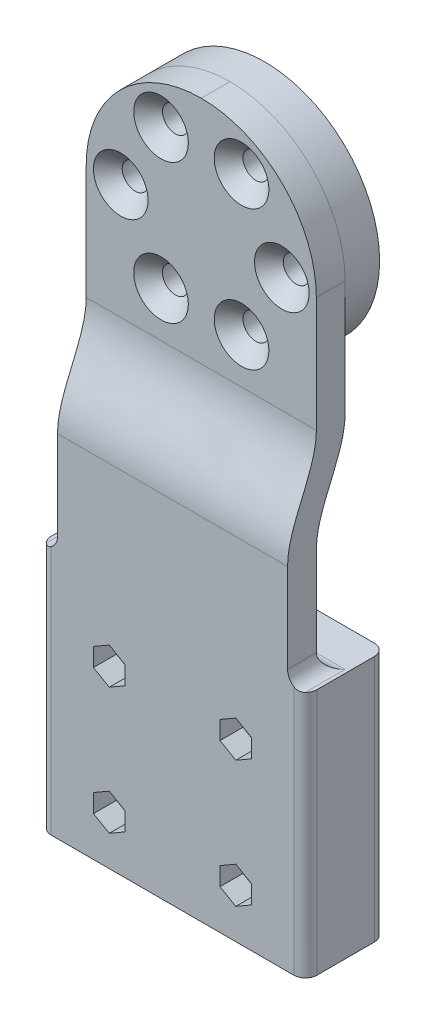
SolidWorks part; units mm, degrees
other "Markup1"
sketch "Sketch13" plane through (20, -53, 11) normal (0.0614, -0.6805, 0.7302) x (0.9699, -0.1321, -0.2046)
ref_plane "Front Plane" through (0, 0, 0) normal (0, 0, 1) x (1, 0, 0)
ref_plane "Top Plane" through (0, 0, 0) normal (0, 1, 0) x (1, 0, 0)
ref_plane "Right Plane" through (0, 0, 0) normal (1, 0, 0) x (0, 0, -1)
sketch "Sketch7" plane through (0, 0, 0) normal (0, 0, 1) x (1, 0, 0)
  line L1 (-20, 20) -> (20, 20)
  line L2 (-20, 20) -> (-20, -20)
  line L3 (-20, -20) -> (20, -20)
  line L4 (20, 20) -> (20, -20)
  line L5 (-20, 20) -> (20, -20) construction
  line L6 (-20, -20) -> (20, 20) construction
  point P0 (0, 0)
extrude "Boss-Extrude1" add sketch "Sketch7" along normal blind 11
ref_plane "Plane2" through (0, -21.4103, 5.7369) normal (0, -0.9659, 0.2588) x (1, 0, 0)
sketch "Sketch8" plane through (0, -20, 2.0782) normal (0, -1, 0) x (1, 0, 0)
  line L0 (20, 8.9218) -> (20, -2.0782) construction
  line L1 (-20, 8.9218) -> (20, 8.9218)
  line L2 (-20, 8.9218) -> (-20, 3.9218)
  line L3 (-20, 3.9218) -> (20, 3.9218)
  line L4 (20, 8.9218) -> (20, 3.9218)
  line L5 (0, 3.9218) -> (0, 8.9218) construction
  line L6 (-20, 6.4218) -> (20, 6.4218) construction
  line L7 (-20, -2.0782) -> (20, -2.0782) construction
  point P764 (0, 6.4218)
  dimension "D1" = 6
ref_plane "Plane4" through (0, -38, 0) normal (0, -1, 0) x (-1, 0, 0)
sketch "Sketch19" plane through (0, -38, 0) normal (0, -1, 0) x (-1, 0, 0)
  line L0 (20, -11) -> (20, 0) construction
  line L1 (20, -16) -> (-20, -16)
  line L2 (20, -16) -> (20, -11)
  line L3 (20, -11) -> (-20, -11)
  line L4 (-20, -16) -> (-20, -11)
  line L5 (20, -16) -> (-20, -11) construction
  line L6 (20, -11) -> (-20, -16) construction
  line L7 (-20, -11) -> (-20, 0) construction
  line L8 (20, -11) -> (-20, -11) construction
  point P4 (0, -13.5)
  dimension "D1" = 5
  dimension "D2" = 5
loft "Loft1" add profiles "Sketch19", "Sketch8" start constraint normal to profile start tangent length 1 end constraint normal to profile end tangent length 1 connector at (-20, -38, 16) connector at (-20, -20, 11)
sketch "Sketch16" plane through (0, 0, 0) normal (0, 0, -1) x (-1, 0, 0)
  line L1 (24.5131, 32.6211) -> (-24.5131, 32.6211)
  line L2 (24.5131, 32.6211) -> (24.5131, -32.6211)
  line L3 (24.5131, -32.6211) -> (-24.5131, -32.6211)
  line L4 (-24.5131, 32.6211) -> (-24.5131, -32.6211)
  line L5 (24.5131, 32.6211) -> (-24.5131, -32.6211) construction
  line L6 (24.5131, -32.6211) -> (-24.5131, 32.6211) construction
  circle A0 centre (0, 0) radius 20
extrude "Cut-Extrude3" cut sketch "Sketch16" against normal blind 6
ref_plane "Plane3" [suppressed] through (0, -56, 0) normal (0, -1, 0) x (-1, 0, 0)
sketch "Sketch17" plane through (0, -38, 0) normal (0, -1, 0) x (-1, 0, 0)
  line L1 (20, -16) -> (-20, -16)
  line L2 (20, -16) -> (20, -11)
  line L3 (20, -11) -> (-20, -11)
  line L4 (-20, -16) -> (-20, -11)
  line L5 (20, -16) -> (-20, -11) construction
  line L6 (20, -11) -> (-20, -16) construction
  line L10 (-20, -16) -> (20, -16) construction
  line L11 (-20, -6) -> (-20, -11) construction
  line L12 (20, -11) -> (20, -6) construction
  point P4 (0, -13.5)
  dimension "D1" = 5
extrude "Boss-Extrude5" add sketch "Sketch17" along normal blind 18
sketch "Sketch10" plane through (0, 0, 11) normal (0, 0, 1) x (1, 0, 0)
  circle A0 centre (-7.0001, 12.1244) radius 2.25
  circle A1 centre (6.9999, 12.1244) radius 2.25
  circle A2 centre (13.9999, 0.0001) radius 2.25
  circle A3 centre (6.9999, -12.1243) radius 2.25
  circle A4 centre (-7.0001, -12.1243) radius 2.25
  circle A5 centre (-14.0001, 0.0001) radius 2.25
  point P0 (0, 0)
  point P1 (0.0025, 0.0011)
  dimension "D4" = 4.5
extrude "Cut-Extrude1" cut sketch "Sketch10" against normal blind 25
sketch "Sketch11" plane through (0, -56, -3.473) normal (0, 1, 0) x (1, 0, 0)
  line L0 (20, -19.473) -> (-20, -19.473) construction
  line L5 (23.1, -5.473) -> (-23.1, -5.473)
  line L6 (23.1, -5.473) -> (23.1, -19.473)
  line L7 (23.1, -19.473) -> (-23.1, -19.473)
  line L8 (-23.1, -5.473) -> (-23.1, -19.473)
  line L9 (23.1, -5.473) -> (-23.1, -19.473) construction
  line L10 (23.1, -19.473) -> (-23.1, -5.473) construction
  line L16 (20, -14.473) -> (20, -19.473) construction
  point P0 (0, -12.473)
  point P7 (0, 0)
  point P8 (0, 0)
  point P9 (0, 0)
  dimension "D1" = 46.2
  dimension "D2" = 3.1
  dimension "D3" = 14
chamfer "Chamfer1" distance 2.5 angle 45 6 edges at (-4.7501, 12.1244, 11) (-11.7501, 0.0001, 11) (-4.7501, -12.1243, 11) (9.2499, 12.1244, 11) (16.2499, 0.0001, 11) (9.2499, -12.1243, 11)
fillet "Fillet3" radius 20 2 edges at (20, 20, 8.5) (-20, 20, 8.5)
extrude "Boss-Extrude6" add sketch "Sketch11" against normal blind 43
fillet "Fillet9" radius 2.5 3 edges at (0, -56, 11) (-20, -56, 13.5) (20, -56, 13.5)
ref_plane "Plane5" through (0, -99, 0) normal (0, -1, 0) x (-1, 0, 0)
sketch "Sketch20" plane through (0, -99, 0) normal (0, -1, 0) x (1, 0, 0)
  line L0 (0, 2) -> (0, 16) construction
  line L1 (20.3, 6.8) -> (-20.3, 6.8)
  line L2 (20.3, 6.8) -> (20.3, 11.2)
  line L3 (20.3, 11.2) -> (-20.3, 11.2)
  line L4 (-20.3, 6.8) -> (-20.3, 11.2)
  line L5 (20.3, 6.8) -> (-20.3, 11.2) construction
  line L6 (20.3, 11.2) -> (-20.3, 6.8) construction
  line L7 (23.1, 2) -> (-23.1, 2) construction
  line L8 (-23.1, 16) -> (23.1, 16) construction
  line L9 (-23.1, 2) -> (-23.1, 16) construction
  point P0 (0, 9)
  dimension "D1" = 4.4
  dimension "D2" = 40.6
  dimension "D3" = 23.1
  dimension "D4" = 7
extrude "Cut-Extrude4" cut sketch "Sketch20" against normal blind 40
sketch "Sketch22" plane through (0, 0, 0) normal (0, 0, 1) x (1, 0, 0)
  line L0 (-7.7, -99) -> (7.7, -99) construction
  line L1 (20, -99) -> (-20, -99)
  line L2 (20, -99) -> (20, -59)
  line L3 (20, -59) -> (-20, -59)
  line L4 (-20, -99) -> (-20, -59)
  line L5 (20, -99) -> (-20, -59) construction
  line L6 (20, -59) -> (-20, -99) construction
  line L9 (23.1, -99) -> (23.1, -56) construction
  circle A0 centre (-11, -68.5) radius 1.7
  circle A1 centre (11, -68.5) radius 1.7
  circle A2 centre (11, -90.5) radius 1.7
  circle A3 centre (-11, -90.5) radius 1.7
  point P0 (0, -79)
  point P7 (0, 0)
  point P10 (0, 0)
  point P11 (0, 0)
  point P14 (0, 0)
  dimension "D4" = 3.4
  dimension "D1" = 40
  dimension "D2" = 40
  dimension "D3" = 23.1
  dimension "D5" = 9.5
  dimension "D6" = 8.5
  dimension "D7" = 9
  dimension "D8" = 9
  dimension "D9" = 8.5
  dimension "D10" = 9
  dimension "D11" = 22
extrude "Cut-Extrude5" cut sketch "Sketch22" along normal blind 30 contours A1 | A2 | A3 | A0 region at (-11, -68.5, 0) region at (11, -68.5, 0) region at (11, -90.5, 0) region at (-11, -90.5, 0)
fillet "Fillet11" radius 2 4 edges at (-23.1, -77.5, 16) (-23.1, -77.5, 2) (23.1, -77.5, 16) (23.1, -77.5, 2)
ref_plane "Plane6" through (0, 0, 16) normal (0, 0, 1) x (1, 0, 0)
sketch "Sketch23" plane through (0, 0, 16) normal (0, 0, 1) x (1, 0, 0)
  line L0 (-13.75, -66.9123) -> (-8.25, -70.0877) construction
  line L1 (-11, -65.3246) -> (-13.75, -66.9123)
  line L2 (-13.75, -66.9123) -> (-13.75, -70.0877)
  line L3 (-13.75, -70.0877) -> (-11, -71.6754)
  line L4 (-11, -71.6754) -> (-8.25, -70.0877)
  line L5 (-8.25, -70.0877) -> (-8.25, -66.9123)
  line L6 (-8.25, -66.9123) -> (-11, -65.3246)
  line L7 (-11, -65.3246) -> (-11, -71.6754) construction
  line L8 (11, -65.3246) -> (11, -71.6754) construction
  line L9 (11, -65.3246) -> (8.25, -66.9123)
  line L10 (8.25, -66.9123) -> (8.25, -70.0877)
  line L11 (8.25, -70.0877) -> (11, -71.6754)
  line L12 (11, -71.6754) -> (13.75, -70.0877)
  line L13 (13.75, -70.0877) -> (13.75, -66.9123)
  line L14 (13.75, -66.9123) -> (11, -65.3246)
  line L15 (11, -87.3246) -> (8.25, -88.9123)
  line L16 (8.25, -88.9123) -> (8.25, -92.0877)
  line L17 (8.25, -92.0877) -> (11, -93.6754)
  line L18 (11, -93.6754) -> (13.75, -92.0877)
  line L19 (13.75, -92.0877) -> (13.75, -88.9123)
  line L20 (13.75, -88.9123) -> (11, -87.3246)
  line L21 (-11, -87.3246) -> (-13.75, -88.9123)
  line L22 (-13.75, -88.9123) -> (-13.75, -92.0877)
  line L23 (-13.75, -92.0877) -> (-11, -93.6754)
  line L24 (-11, -93.6754) -> (-8.25, -92.0877)
  line L25 (-8.25, -92.0877) -> (-8.25, -88.9123)
  line L26 (-8.25, -88.9123) -> (-11, -87.3246)
  line L27 (11, -87.3246) -> (11, -94.13) construction
  line L28 (-11, -87.3246) -> (-11, -93.6754) construction
  circle A0 centre (-11, -68.5) radius 2.75 construction
  circle A1 centre (11, -68.5) radius 2.75 construction
  circle A2 centre (11, -90.5) radius 2.75 construction
  circle A3 centre (-11, -90.5) radius 2.75 construction
  point P28 (-13.75, -90.5)
  dimension "D1" = 5.5
  dimension "D2" = 60
  dimension "D3" = 5.5
  dimension "D4" = 5.5
  dimension "D5" = 5.5
extrude "Cut-Extrude6" cut sketch "Sketch23" against normal blind 4
ref_plane "Plane7" through (0, 0, 2) normal (0, 0, -1) x (-1, 0, 0)
sketch "Sketch24" plane through (0, 0, 2) normal (0, 0, -1) x (-1, 0, 0)
  circle A0 centre (-11, -68.5) radius 3
  circle A1 centre (11, -68.5) radius 3
  circle A2 centre (11, -90.5) radius 3
  circle A3 centre (-11, -90.5) radius 3
  dimension "D1" = 6
  dimension "D2" = 6
  dimension "D3" = 6
  dimension "D4" = 6
extrude "Cut-Extrude7" cut sketch "Sketch24" against normal blind 3 contours A1 | A2 | A3 | A0
